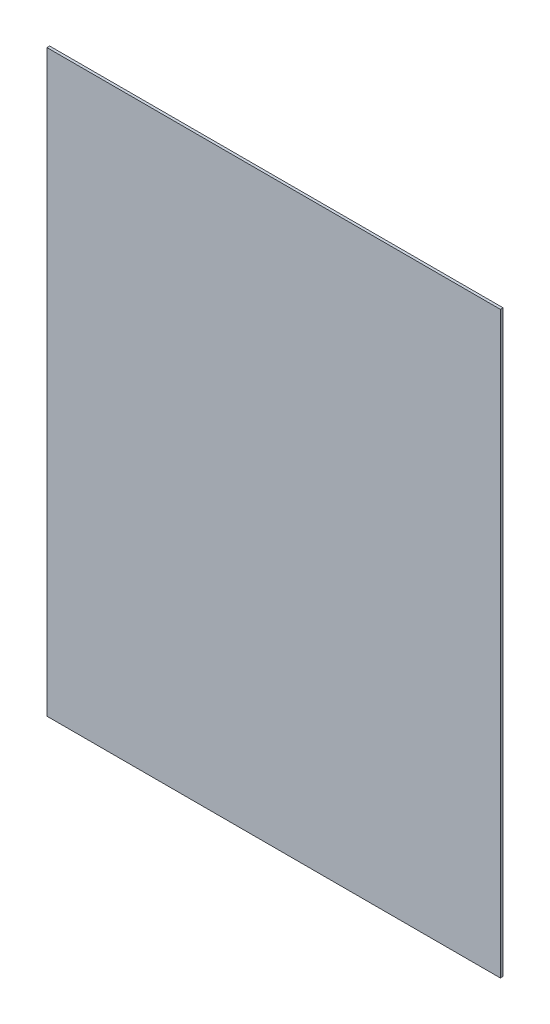
SolidWorks part; units mm, degrees
ref_plane "Přední rovina" through (0, 0, 0) normal (0, 0, 1) x (1, 0, 0)
ref_plane "Horní rovina" through (0, 0, 0) normal (0, 1, 0) x (1, 0, 0)
ref_plane "Pravá rovina" through (0, 0, 0) normal (1, 0, 0) x (0, 0, -1)
sketch "Skica1" plane through (0, 0, 0) normal (0, 0, 1) x (1, 0, 0)
  line L1 (-252.5, 322.5) -> (252.5, 322.5)
  line L2 (-252.5, 322.5) -> (-252.5, -322.5)
  line L3 (-252.5, -322.5) -> (252.5, -322.5)
  line L4 (252.5, 322.5) -> (252.5, -322.5)
  line L5 (-252.5, 322.5) -> (252.5, -322.5) construction
  line L6 (-252.5, -322.5) -> (252.5, 322.5) construction
  point P0 (0, 0)
  dimension "D1" = 505
  dimension "D2" = 645
extrude "Přidat vysunutím1" add sketch "Skica1" along normal blind 3
